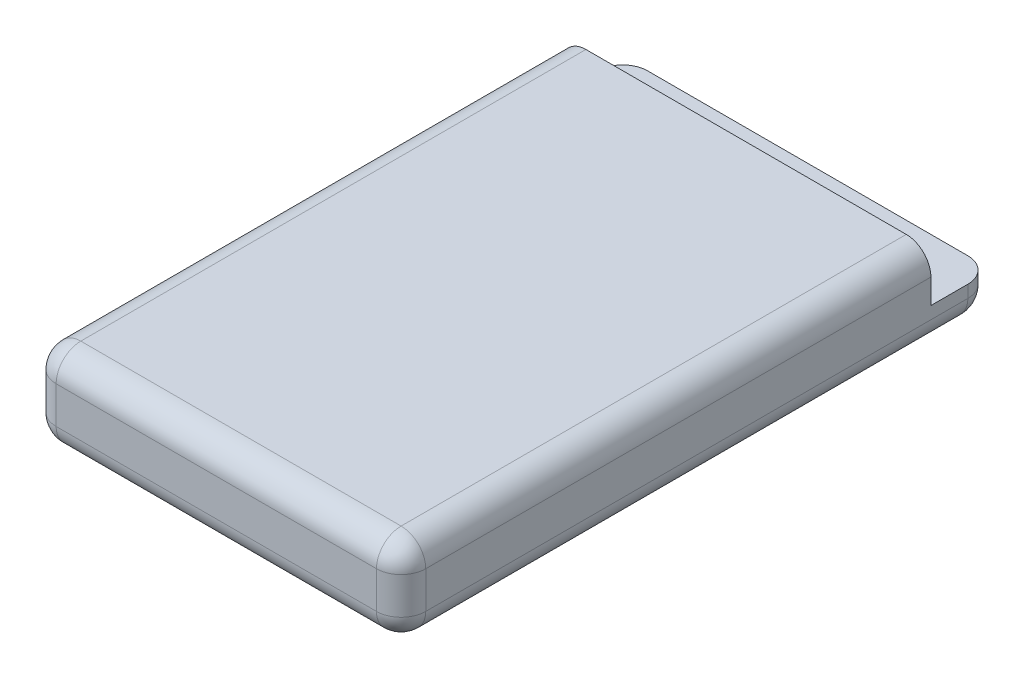
SolidWorks part; units mm, degrees
ref_plane "Спереди" through (0, 0, 0) normal (0, 0, 1) x (1, 0, 0)
ref_plane "Сверху" through (0, 0, 0) normal (0, 1, 0) x (1, 0, 0)
ref_plane "Справа" through (0, 0, 0) normal (1, 0, 0) x (0, 0, -1)
sketch "Эскиз1" plane through (0, 0, 0) normal (0, 1, 0) x (1, 0, 0)
  line L1 (-15, -24) -> (15, -24)
  line L2 (-15, -24) -> (-15, 24)
  line L3 (-15, 24) -> (15, 24)
  line L4 (15, -24) -> (15, 24)
  line L5 (-15, -24) -> (15, 24) construction
  line L6 (-15, 24) -> (15, -24) construction
  point P0 (0, 0)
  dimension "D1" = 48
  dimension "D2" = 30
extrude "Бобышка-Вытянуть1" add sketch "Эскиз1" along normal blind 7
fillet "Скругление1" radius 2 8 edges at (0, 0, -24) (-15, 0, 0) (0, 0, 24) (15, 0, 0) (0, 7, 24) (-15, 7, 0) (0, 7, -24) (15, 7, 0)
fillet "Скругление2" radius 2 12 edges at (14.4142, 6.4142, -23.4142) (14.4142, 0.5858, -23.4142) (14.4142, 6.4142, 23.4142) (14.4142, 0.5858, 23.4142) (-14.4142, 6.4142, -23.4142) (-14.4142, 0.5858, -23.4142) (-14.4142, 6.4142, 23.4142) (-14.4142, 0.5858, 23.4142) (15, 3.5, -24) (15, 3.5, 24) (-15, 3.5, -24) (-15, 3.5, 24)
sketch "Эскиз2" plane through (0, 7, 0) normal (0, 1, 0) x (1, 0, 0)
  line L1 (-15.5748, 24) -> (18.279, 24)
  line L2 (-15.5748, 24) -> (-15.5748, 19)
  line L3 (-15.5748, 19) -> (18.279, 19)
  line L4 (18.279, 24) -> (18.279, 19)
  line L5 (-13, 24) -> (13, 24) construction
  line L6 (-13, 24) -> (13, 24)
  line M5 (-13, 22) -> (-13, -22)
  line M7 (13, -22) -> (13, 22)
  line M8 (13, 22) -> (-13, 22)
  dimension "D1" = 5
extrude "Вырез-Вытянуть1" cut sketch "Эскиз2" against normal blind 4 contours L3 M5 M7 M8 | L4 L1 L2 L3 M5 M8 M7 region at (2.5076, 7, -22.3546) region at (0, 7, -20.5)
